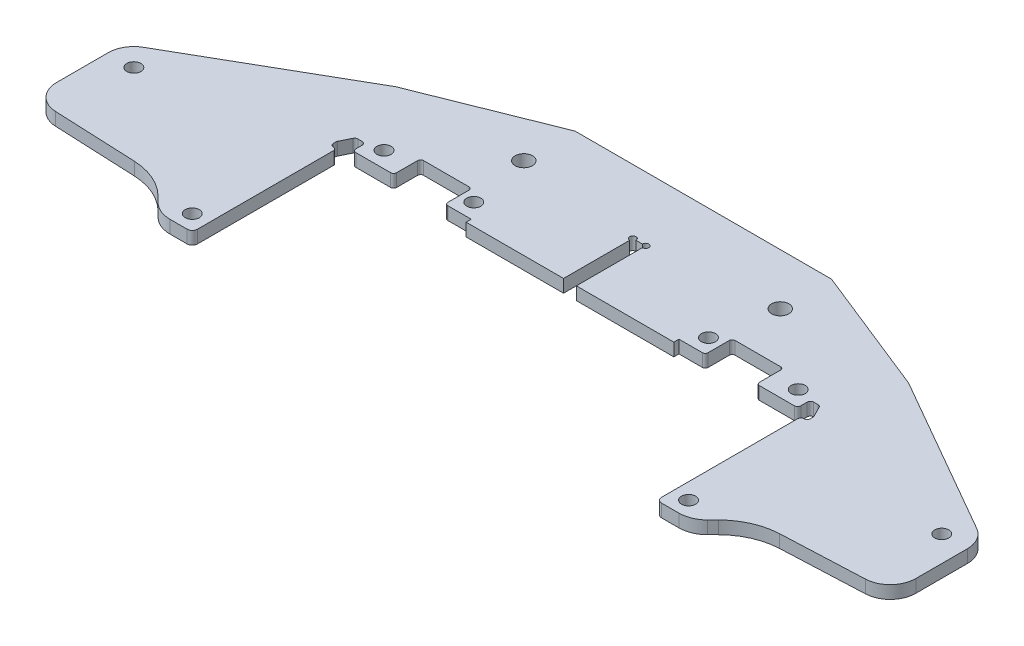
SolidWorks part; units mm, degrees
ref_plane "前视基准面" through (0, 0, 0) normal (0, 0, 1) x (1, 0, 0)
ref_plane "上视基准面" through (0, 0, 0) normal (0, 1, 0) x (1, 0, 0)
ref_plane "右视基准面" through (0, 0, 0) normal (1, 0, 0) x (0, 0, -1)
sketch "草图1" plane through (0, 0, 0) normal (0, 1, 0) x (1, 0, 0)
  line L0 (-20, 0) -> (20, 0)
  line L2 (0, -40) -> (60, -40)
  line L3 (60, -40) -> (60, -20)
  line L4 (60, -20) -> (20, 0)
  line L5 (0, -40) -> (-60, -40)
  line L6 (-60, -40) -> (-60, -20)
  line L7 (-60, -20) -> (-20, 0)
  point P4 (0, 0)
extrude "凸台-拉伸1" add sketch "草图1" along normal blind 2
sketch "草图2" plane through (0, 2, 0) normal (0, 1, 0) x (1, 0, 0)
  line L1 (0, -20) -> (13.2, -20)
  line L2 (13.2, -20) -> (13.2, -40)
  line L3 (-60, -40) -> (60, -40) construction
  line L4 (13.2, -40) -> (-13.2, -40)
  line L5 (-13.2, -40) -> (-13.2, -20)
  line L6 (-13.2, -20) -> (0, -20)
extrude "切除-拉伸1" cut sketch "草图2" against normal blind 10
sketch "草图3" plane through (0, 2, 0) normal (0, 1, 0) x (1, 0, 0)
  line L3 (1, -10) -> (-1, -10)
  line L6 (-1, -10) -> (-1, -20)
  line L7 (13.2, -20) -> (-13.2, -20) construction
  line L8 (-1, -20) -> (1, -20)
  line L9 (1, -20) -> (1, -10)
extrude "切除-拉伸2" cut sketch "草图3" against normal blind 10
sketch "草图4" plane through (0, 2, 0) normal (0, 1, 0) x (1, 0, 0)
  line L0 (-60, -40) -> (-60, -38)
  line L1 (-60, -20) -> (-60, -40) construction
  line L2 (-60, -40) -> (-15, -40)
  line L3 (-60, -40) -> (-13.2, -40) construction
  line L4 (-15, -40) -> (-60, -38)
  line L5 (60, -40) -> (15, -40)
  line L6 (13.2, -40) -> (60, -40) construction
  line L7 (15, -40) -> (60, -38)
  line L8 (60, -40) -> (60, -20) construction
  line L9 (60, -38) -> (60, -40)
extrude "切除-拉伸3" cut sketch "草图4" against normal blind 10
sketch "草图5" plane through (0, 2, 0) normal (0, 1, 0) x (1, 0, 0)
  line L0 (13.2, -20) -> (36.2, -20)
  line L1 (36.2, -20) -> (36.2, -42.4846)
  line L2 (36.2, -42.4846) -> (13.2, -42.4846)
  line L3 (13.2, -42.4846) -> (13.2, -20)
  line L4 (0, 0) -> (0, -5.9523) construction
  line L5 (-13.2, -42.4846) -> (-13.2, -20)
  line L6 (-36.2, -42.4846) -> (-13.2, -42.4846)
  line L7 (-36.2, -20) -> (-36.2, -42.4846)
  line L8 (-13.2, -20) -> (-36.2, -20)
extrude "切除-拉伸4" cut sketch "草图5" against normal blind 10
sketch "草图6" plane through (0, 2, 0) normal (0, 1, 0) x (1, 0, 0)
  line L1 (36.2, -20) -> (1, -20) construction
  line L2 (16.2, -20) -> (16.2, -20.8)
  line L3 (0, 0) -> (0, -6.82) construction
  line L4 (-16.2, -20) -> (-16.2, -20.8)
  line L6 (16.2, -20.8) -> (-16.2, -20.8)
  line L7 (-16.2, -20) -> (16.2, -20)
extrude "凸台-拉伸2" add sketch "草图6" against normal up to surface (2 mm away) up to face at (0, 0, 21.0083)
sketch "草图7" plane through (0, 2, 0) normal (0, 1, 0) x (1, 0, 0)
  line L0 (0, 0) -> (0, -4.4643) construction
  circle A0 centre (32.3, -17.5) radius 1.1
  circle A1 centre (18.3, -17.5) radius 1.1
  circle A2 centre (-18.3, -17.5) radius 1.1
  circle A3 centre (-32.3, -17.5) radius 1.1
extrude "切除-拉伸5" cut sketch "草图7" against normal blind 10
sketch "草图8" plane through (0, 2, 0) normal (0, 1, 0) x (1, 0, 0)
  line L0 (0, 0) -> (0, 20.0963) construction
  line L1 (-36.2, -43.5) -> (-36.2, -40)
  line L2 (36.2, -40) -> (36.2, -35.5)
  line L3 (36.2, -39.0578) -> (36.2, -20) construction
  line L4 (36.2, -35.5) -> (41.2, -35.5)
  line L5 (41.2, -35.5) -> (41.2, -43.5)
  line L6 (41.2, -43.5) -> (36.2, -43.5)
  line L7 (36.2, -43.5) -> (36.2, -40)
  line L8 (-41.2, -43.5) -> (-36.2, -43.5)
  line L9 (-41.2, -35.5) -> (-41.2, -43.5)
  line L10 (-36.2, -35.5) -> (-41.2, -35.5)
  line L11 (-36.2, -40) -> (-36.2, -35.5)
extrude "凸台-拉伸3" add sketch "草图8" against normal up to surface (2 mm away) up to face at (-32.3, 0, 16.4)
sketch "草图9" plane through (0, 2, 0) normal (0, 1, 0) x (1, 0, 0)
  line L0 (0, 0) -> (0, 14.1665) construction
  circle A0 centre (38.7, -41) radius 1.1
  circle A1 centre (-38.7, -41) radius 1.1
extrude "切除-拉伸6" cut sketch "草图9" against normal blind 10
chamfer "倒角2" distance 5 angle 45 2 edges at (-41.2, 1, 38.8356) (41.2, 1, 38.8356) first distance on face at (-41.2, 1, 41.1678) first distance on face at (41.2, 1, 41.1678)
fillet "圆角2" radius 10 2 edges at (46.4326, 1, 38.603) (-46.4326, 1, 38.603)
fillet "圆角3" radius 4.5 2 edges at (-41.5356, 1, 43.5) (41.5356, 1, 43.5)
sketch "草图10" plane through (0, 2, 0) normal (0, 1, 0) x (1, 0, 0)
  line L0 (36.2, -20) -> (36.2, -18)
  line L1 (36.2, -18) -> (34.7, -18)
  line L2 (34.7, -18) -> (34.7, -20)
  line L3 (36.2, -20) -> (16.2, -20) construction
  line L4 (34.7, -20) -> (36.2, -20)
  line L5 (0, 0) -> (0, -4.6008) construction
  line L6 (-34.7, -20) -> (-36.2, -20)
  line L7 (-34.7, -18) -> (-34.7, -20)
  line L8 (-36.2, -18) -> (-34.7, -18)
  line L9 (-36.2, -20) -> (-36.2, -18)
extrude "切除-拉伸7" cut sketch "草图10" against normal blind 10
sketch "草图11" plane through (0, 2, 0) normal (0, 1, 0) x (1, 0, 0)
  circle A0 centre (20, -8) radius 1.35
  circle A1 centre (-20, -8) radius 1.35
extrude "切除-拉伸8" cut sketch "草图11" against normal blind 10
sketch "草图12" plane through (0, 2, 0) normal (0, 1, 0) x (1, 0, 0)
  line L0 (0, 0) -> (0, -6.8434) construction
  line L1 (-20.3, -20) -> (-20.3, -15.8)
  line L2 (-16.2, -20) -> (-34.7, -20) construction
  line L3 (-20.3, -15.8) -> (-28.3, -15.8)
  line L4 (-28.3, -15.8) -> (-28.3, -20)
  line L5 (-28.3, -20) -> (-20.3, -20)
  line L6 (28.3, -20) -> (20.3, -20)
  line L7 (28.3, -15.8) -> (28.3, -20)
  line L8 (20.3, -15.8) -> (28.3, -15.8)
  line L9 (20.3, -20) -> (20.3, -15.8)
extrude "切除-拉伸9" cut sketch "草图12" against normal blind 10
fillet "圆角5" radius 0.45 8 edges at (-20.3, 1, 15.8) (-28.3, 1, 15.8) (28.3, 1, 20) (20.3, 1, 20) (-20.3, 1, 20) (-28.3, 1, 20) (28.3, 1, 15.8) (20.3, 1, 15.8)
sketch "草图13" plane through (0, 2, 0) normal (0, 1, 0) x (1, 0, 0)
  line L0 (-36.2, -18) -> (-36.2, -20)
  line L1 (-36.2, -18) -> (-36.2, -43.5) construction
  line L3 (-37.2, -20) -> (-36.2, -18)
  line L4 (-37.2, -20) -> (-37.2, -21)
  line L5 (-37.2, -21) -> (-36.2, -21)
  line L6 (-36.2, -21) -> (-36.2, -20)
  line L7 (0, 0) -> (0, -3.2185) construction
  line L8 (36.2, -21) -> (36.2, -20)
  line L9 (37.2, -21) -> (36.2, -21)
  line L10 (37.2, -20) -> (37.2, -21)
  line L11 (37.2, -20) -> (36.2, -18)
  line L12 (36.2, -18) -> (36.2, -20)
extrude "切除-拉伸10" cut sketch "草图13" against normal blind 10
fillet "圆角6" radius 0.5 12 edges at (34.7, 1, 18) (34.7, 1, 20) (36.2, 1, 18) (37.2, 1, 20) (37.2, 1, 21) (36.2, 1, 21) (-34.7, 1, 20) (-34.7, 1, 18) (-36.2, 1, 18) (-37.2, 1, 20) (-36.2, 1, 21) (-37.2, 1, 21)
fillet "圆角7" radius 0.8 2 edges at (-36.2, 1, 43.5) (36.2, 1, 43.5)
sketch "草图14" plane through (0, 2, 0) normal (0, 1, 0) x (1, 0, 0)
  circle A0 centre (-1, -10) radius 0.5
  circle A1 centre (1, -10) radius 0.5
extrude "切除-拉伸11" cut sketch "草图14" against normal blind 10
sketch "草图15" plane through (0, 2, 0) normal (0, 1, 0) x (1, 0, 0)
  line L0 (-1, -20) -> (-1, -20.8)
  line L1 (-16.2, -20.8) -> (16.2, -20.8) construction
  line L2 (-1, -20.8) -> (1, -20.8)
  line L3 (1, -20.8) -> (1, -20)
  line L4 (1, -20) -> (-1, -20)
extrude "切除-拉伸12" cut sketch "草图15" against normal blind 10
sketch "草图16" plane through (0, 2, 0) normal (0, 1, 0) x (1, 0, 0)
  line L0 (-60, -20) -> (-60, -38)
  line L3 (-60, -38) -> (-67, -37.6889)
  line L4 (-67, -37.6889) -> (-67, -23.5)
  line L5 (0, 0) -> (0, -26.1768) construction
  line L6 (20, 0) -> (-20, 0) construction
  line L11 (-60, -20) -> (-20, 0)
  line L14 (-40, -8) -> (-20, 0)
  line L15 (-40, -8) -> (-67, -23.5)
  line L16 (40, -8) -> (67, -23.5)
  line L17 (40, -8) -> (20, 0)
  line L18 (60, -20) -> (20, 0)
  line L19 (67, -37.6889) -> (67, -23.5)
  line L20 (60, -38) -> (67, -37.6889)
  line L21 (60, -20) -> (60, -38)
extrude "凸台-拉伸4" add sketch "草图16" against normal blind 2
fillet "圆角8" radius 4 4 edges at (67, 1, 37.6889) (67, 1, 23.5) (-67, 1, 37.6889) (-67, 1, 23.5)
sketch "草图17" plane through (0, 2, 0) normal (0, 1, 0) x (1, 0, 0)
  circle A0 centre (-63, -25.816) radius 1.1
  circle A1 centre (63, -25.816) radius 1.1
extrude "切除-拉伸13" cut sketch "草图17" against normal blind 10
